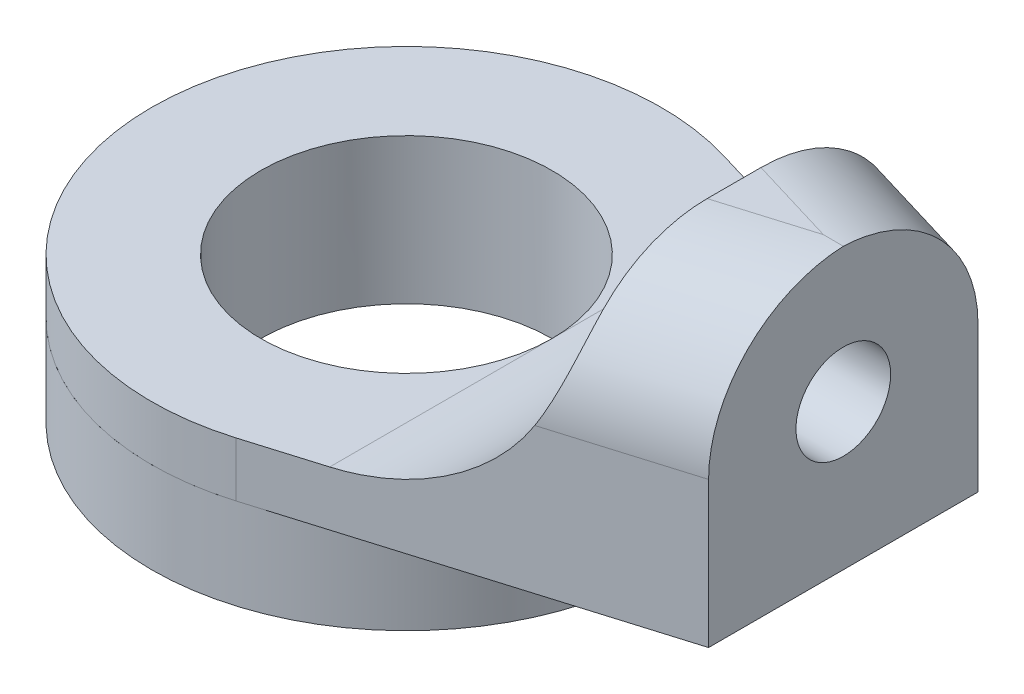
SolidWorks part; units mm, degrees
ref_plane "Спереди" through (0, 0, 0) normal (0, 0, 1) x (1, 0, 0)
ref_plane "Сверху" through (0, 0, 0) normal (0, 1, 0) x (1, 0, 0)
ref_plane "Справа" through (0, 0, 0) normal (1, 0, 0) x (0, 0, -1)
sketch "Эскиз1" plane through (0, 0, 0) normal (0, 1, 0) x (1, 0, 0)
  circle A0 centre (0, 0) radius 7
extrude "Бобышка-Вытянуть1" add sketch "Эскиз1" along normal blind 1.5
sketch "Эскиз3" plane through (0, 1.5, 0) normal (0, 1, 0) x (1, 0, 0)
  circle A0 centre (0, 0) radius 4
  dimension "D1" = 8
extrude "Вырез-Вытянуть2" cut sketch "Эскиз3" against normal through all from surface at 0 starting at face at (0, 1.5, 7)
sketch "Эскиз5" plane through (0, 1.5, 0) normal (0, 1, 0) x (1, 0, 0)
  line L0 (0, 0) -> (12, 0) construction
  line L1 (12, -3.7) -> (12, 3.7)
  line L2 (12, -3.7) -> (2.0171, -6.7037)
  line L3 (12, 3.7) -> (2.0171, 6.7037)
  circle A0 centre (0, 0) radius 7 construction
  circle A1 centre (0, 0) radius 7.0006
  arc A2 (4.3301, -5.5) -> (0.6829, 6.9666) centre (0, 0) ccw
  dimension "D1" = 12
  dimension "D2" = 3.7
extrude "Бобышка-Вытянуть2" add sketch "Эскиз5" against normal blind 1.5
sketch "Эскиз11" plane through (0, 0, 0) normal (0, -1, 0) x (-1, 0, 0)
  circle A0 centre (0, 0) radius 7
  circle A1 centre (0, 0) radius 4
extrude "Бобышка-Вытянуть4" add sketch "Эскиз11" along normal blind 2.5
sketch "Эскиз13" plane through (0, 1.5, 0) normal (0, 1, 0) x (1, 0, 0)
  line L1 (12, -3.7) -> (12, 3.7) construction
  line L2 (9, 0) -> (9, 4.6027)
  line L3 (12, 3.7) -> (2.0171, 6.7037) construction
  line L4 (9, 4.6027) -> (12, 3.7)
  line L5 (12, 3.7) -> (12, -3.7)
  line L6 (9, 0) -> (9, -4.6027)
  line L7 (12, -3.7) -> (2.0171, -6.7037) construction
  line L8 (9, -4.6027) -> (12, -3.7)
  line L9 (12, -3.7) -> (11.9975, -3.6997)
  dimension "D1" = 3
extrude "Бобышка-Вытянуть6" add sketch "Эскиз13" along normal blind 6.2
fillet "Скругление1" radius 5 1 edges
sketch "Эскиз12" plane through (12, 0, 0) normal (1, 0, 0) x (0, 0, -1)
  line L0 (0, 1.5) -> (0, 4) construction
  line L1 (-3.7, 1.5) -> (3.7, 1.5) construction
  line L2 (0, -2.5) -> (0, 1.5) construction
  line L3 (0, 0) -> (0, 1.5) construction
  line L4 (-3.7, 1.5) -> (-3.7, 4)
  line L5 (3.7, 1.5) -> (3.7, 4)
  circle A0 centre (0, 4) radius 1.3
  dimension "D1" = 2.5
extrude "Вырез-Вытянуть3" cut sketch "Эскиз12" against normal through all
fillet "Скругление2" radius 3.7 2 edges at (10.5, 7.7, 4.1513) (10.5, 7.7, -4.1513)
